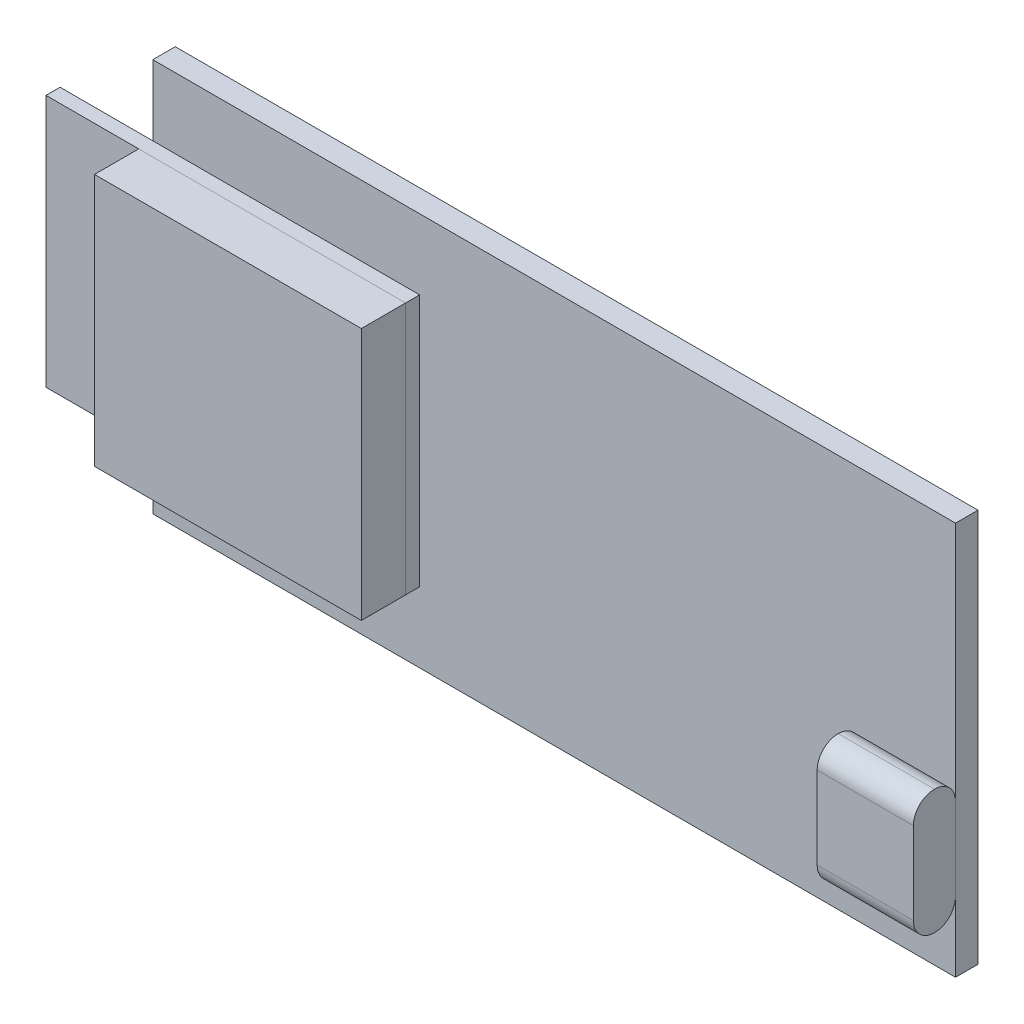
SolidWorks part; units mm, degrees
ref_plane "Front Plane" through (0, 0, 0) normal (1, 0, 0) x (0, 1, 0)
ref_plane "Top Plane" through (0, 0, 0) normal (0, 0, 1) x (0, 1, 0)
ref_plane "Right Plane" through (0, 0, 0) normal (0, 1, 0) x (-1, 0, 0)
sketch "Sketch1" plane through (0, 0, 0) normal (0, 0, 1) x (0, 1, 0)
  line L0 (-0.1709, 57.158) -> (-0.1709, 0.008) construction
  line L2 (902.9971, 1207.013) -> (930.9971, 1207.013)
  line L3 (902.9971, 1207.013) -> (902.9971, 1149.863)
  line L4 (902.9971, 1149.863) -> (930.9971, 1149.863)
  line L5 (930.9971, 1207.013) -> (930.9971, 1149.863)
  line L6 (907.9971, 1213.613) -> (925.9971, 1213.613)
  line L7 (907.9971, 1213.613) -> (907.9971, 1207.013)
  line L8 (907.9971, 1207.013) -> (925.9971, 1207.013)
  line L9 (925.9971, 1213.613) -> (925.9971, 1207.013)
  line L10 (906.4971, 1149.863) -> (915.3471, 1149.863)
  line L11 (906.4971, 1149.863) -> (906.4971, 1156.713)
  line L12 (906.4971, 1156.713) -> (915.3471, 1156.713)
  line L13 (915.3471, 1149.863) -> (915.3471, 1156.713)
  line L14 (907.9971, 1207.013) -> (925.9971, 1207.013)
  line L15 (907.9971, 1207.013) -> (907.9971, 1188.013)
  line L16 (907.9971, 1188.013) -> (925.9971, 1188.013)
  line L17 (925.9971, 1207.013) -> (925.9971, 1188.013)
  dimension "D1" = 57.15
  dimension "D2" = 57.15
  dimension "D3" = 28
  dimension "D4" = 6.6
  dimension "D5" = 18
  dimension "D6" = 57.15
  dimension "D7" = 5
  dimension "D8" = 5
  dimension "D9" = 3.5
  dimension "D10" = 8.85
  dimension "D11" = 6.85
  dimension "D12" = 19
extrude "Boss-Extrude1" add sketch "Sketch1" along normal blind 1.6 contours L3 L4 L5 L2
extrude "Boss-Extrude2" add sketch "Sketch1<4>" along normal blind 3 from surface separate body contours L4 L13 L12 L11 region at (-1153.288, 910.9221, 0) starting at face at (-1178.438, 916.9971, 1.6)
sketch "Sketch1<4>" plane through (0, 0, 0) normal (0, 0, 1) x (0, 1, 0) same geometry as "Sketch1"
fillet "Fillet1" radius 1.5 4 edges at (-1153.288, 906.4971, 1.6) (-1153.288, 915.3471, 1.6) (-1153.288, 915.3471, 4.6) (-1153.288, 906.4971, 4.6)
extrude "Boss-Extrude3" add sketch "Sketch1<5>" along normal blind 1 from surface separate body contours L9 L6 L7 L2 | L17 L2 L15 L16 region at (-1210.313, 916.9971, 0) region at (-1197.513, 916.9971, 0) starting at face at (-1178.438, 916.9971, 1.6)
sketch "Sketch1<5>" plane through (0, 0, 0) normal (0, 0, 1) x (0, 1, 0) same geometry as "Sketch1"
extrude "Boss-Extrude4" add sketch "Sketch1<6>" along normal blind 3.15 from surface separate body contours L17 L2 L15 L16 region at (-1197.513, 916.9971, 0) starting at face at (-1200.813, 916.9971, 2.6)
sketch "Sketch1<6>" plane through (0, 0, 0) normal (0, 0, 1) x (0, 1, 0) same geometry as "Sketch1"
